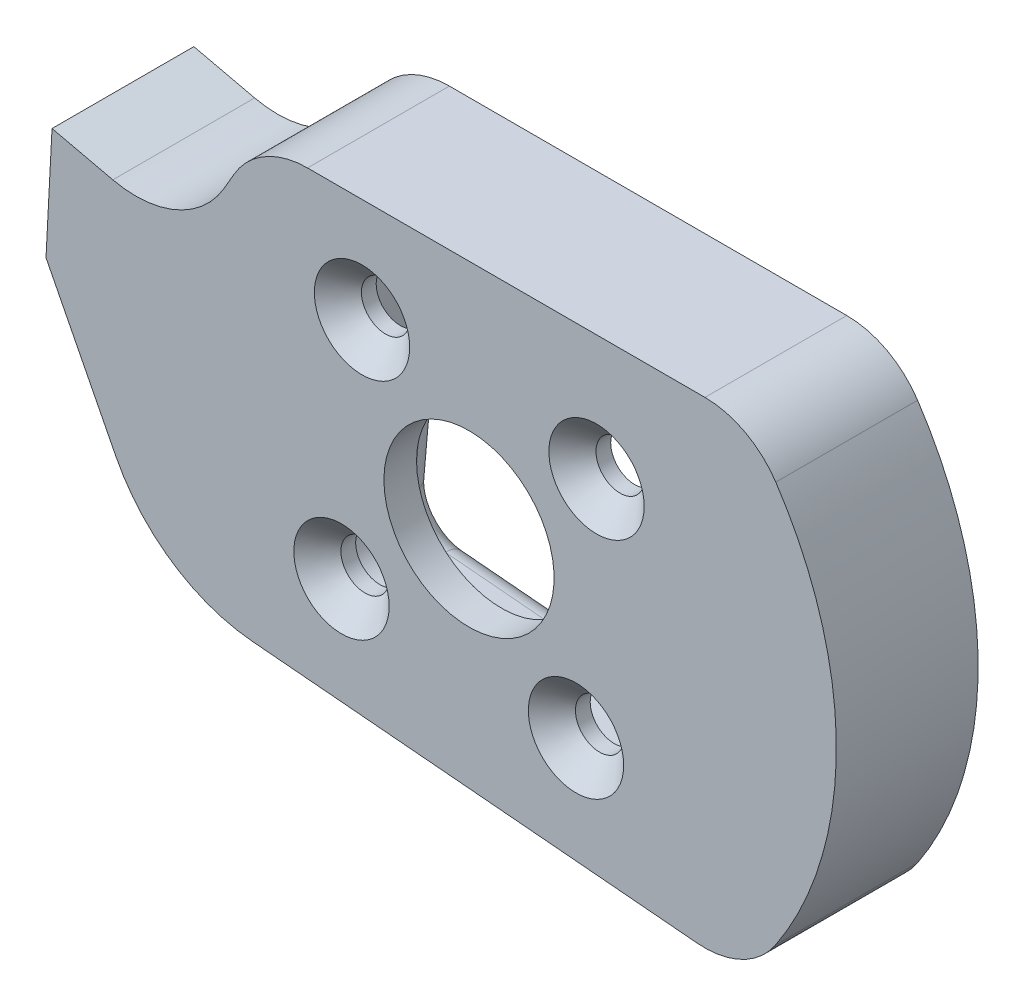
SolidWorks part; units mm, degrees
material "AISI 4340 Aço, normalizado"
ref_plane "Plano frontal" through (0, 0, 0) normal (0, 0, 1) x (1, 0, 0)
ref_plane "Plano superior" through (0, 0, 0) normal (0, 1, 0) x (1, 0, 0)
ref_plane "Plano direito" through (0, 0, 0) normal (1, 0, 0) x (0, 0, -1)
other "Center of Mass"
sketch "Sketch2" plane through (0, 0, 0) normal (0, 0, 1) x (1, 0, 0)
  line L0 (0, 0) -> (-50, 0) construction
  line L1 (-127.5781, 46.0511) -> (-149.0143, 51)
  line L2 (0, 0) -> (-155.9672, 21.9198) construction
  line L5 (-58.9322, 84) -> (81.1804, 84)
  line L6 (0, 0) -> (0, 41.2714) construction
  line L8 (-84.913, 69) -> (-88.303, 63.1284)
  line L14 (-78.3219, -70.2808) -> (78.4896, -84)
  line L19 (-149.0143, 51) -> (-151.1368, 10.5)
  line L20 (-149.5248, 48.7888) -> (-147.8193, 56.1762) construction
  line L22 (-151.1368, 10.5) -> (-126.5529, -37.7485)
  circle A0 centre (0, 0) radius 157.5 construction
  arc A5 (81.1804, 84) -> (106.1589, 70.6154) centre (81.1804, 54) cw
  arc A6 (-58.9322, 84) -> (-84.913, 69) centre (-58.9322, 54) ccw
  arc A17 (-126.5529, -37.7485) -> (-78.3219, -70.2808) centre (-73.0925, -10.5091) ccw
  arc A18 (-127.5781, 46.0511) -> (-88.303, 63.1284) centre (-119.4799, 81.1284) ccw
  arc A20 (106.1589, 70.6154) -> (106.0595, -70.7647) centre (0, 0) cw
  arc A21 (78.4896, -84) -> (106.0595, -70.7647) centre (81.1043, -54.1142) ccw
  point P29 (-157.5, 0)
  point P31 (29.3939, 84)
  point P32 (-76.2527, 84)
  point P33 (106.1589, -70.6154)
  dimension "D1" = 315
  dimension "D4" = 30
  dimension "D5" = 36
  dimension "D13" = 30
  dimension "D11" = 60
  dimension "D10" = 84
  dimension "D2" = 5
  dimension "D3" = 10
  dimension "D7" = 30
  dimension "D8" = 77
  dimension "D12" = 30
  dimension "D9" = 51
  dimension "D14" = 40.5
  dimension "D15" = 22
  dimension "D6" = 30
  dimension "D16" = 5
  dimension "D17" = 84
extrude "EXTRUSÃO PRINCIPAL" add sketch "Sketch2" along normal blind 50 contours L5 A5 A20 A21 L14 A17 L22 L19 L1 A18 L8 A6
other "Ponto de referência do centro da massa1"
ref_plane "Plano2" through (0, 2.2662, 0) normal (0, -1, 0) x (-1, 0, 0)
ref_plane "Plano3" through (-2.0065, 0, 0) normal (1, 0, 0) x (0, 0, -1)
sketch "Esboço2" plane through (0, 0, 0) normal (0, 0, -1) x (-1, 0, 0)
  line L0 (-8.25, 2.2662) -> (8.25, 2.2662) construction
  line L1 (-48.3318, 55.5818) -> (42.3219, 63.513)
  line L2 (-59.2402, 42.5816) -> (-51.3091, -48.0721)
  line L3 (-38.3089, -58.9806) -> (52.3449, -51.0494)
  line L4 (55.3221, 52.6045) -> (63.2533, -38.0492)
  line L5 (-60.2861, 54.5359) -> (64.2992, -50.0035) construction
  line L6 (-50.2632, -60.0265) -> (54.2763, 64.5588) construction
  line L7 (2.0065, 8.25) -> (2.0065, -8.25) construction
  line L8 (78.3219, -70.2808) -> (-78.4896, -84) construction
  line L10 (2.503, 2.2662) -> (86.0271, 2.2662) construction
  circle A0 centre (2.0065, 2.2662) radius 30
  arc A2 (-48.3318, 55.5818) -> (-59.2402, 42.5816) centre (-47.2859, 43.6275) ccw
  arc A3 (42.3219, 63.513) -> (55.3221, 52.6045) centre (43.3678, 51.5586) cw
  arc A4 (52.3449, -51.0494) -> (63.2533, -38.0492) centre (51.299, -39.0951) ccw
  arc A5 (-51.3091, -48.0721) -> (-38.3089, -58.9806) centre (-39.3547, -47.0263) ccw
  circle A6 centre (2.0065, 2.2662) radius 42.5
  circle A7 centre (2.0065, 2.2662) radius 37.5
  circle A8 centre (2.0065, 2.2662) radius 27 construction
  dimension "D1" = 12
  dimension "D5" = 85
  dimension "D6" = 75
  dimension "D7" = 54
  dimension "D3" = 115
  dimension "D4" = 115
  dimension "D2" = 3
extrude "REBAIXO CAMISA" cut sketch "Esboço2" against normal blind 36.5 contours L1 A3 L4 A4 L3 A5 L2 A2
fillet "FILETE ALIVIO REBAIXO" radius 8 8 edges at (56.4784, 51.3409, 0) (55.2747, -2.7453, 0) (47.0682, -56.2188, 0) (-7.018, -55.015, 0) (-60.4915, -46.8085, 0) (-59.2877, 7.2776, 0) (-51.0813, 60.7512, 0) (3.0049, 59.5474, 0)
extrude "FURO EIXO" cut sketch "Esboço2<3>" against normal through all contours A0
sketch "Esboço2<3>" plane through (0, 0, 0) normal (0, 0, -1) x (-1, 0, 0) same geometry as "Esboço2"
extrude "Corte-extrusão1" cut sketch "Esboço2<4>" against normal blind 2 from surface contours A7 starting at face at (-32.0065, 2.2662, 36.5)
sketch "Esboço2<4>" plane through (0, 0, 0) normal (0, 0, -1) x (-1, 0, 0) same geometry as "Esboço2"
sketch "Esboço3" plane through (0, 0, 50) normal (0, 0, 1) x (1, 0, 0)
  line L0 (-78.3219, -70.2808) -> (78.4896, -84) construction
  line L1 (-46.9656, -35.4589) -> (35.7186, -42.6929) construction
  line L2 (-46.9656, -35.4589) -> (-39.7317, 47.2252) construction
  line L3 (-39.7317, 47.2252) -> (42.9525, 39.9913) construction
  line L4 (35.7186, -42.6929) -> (42.9525, 39.9913) construction
  line L5 (-46.9656, -35.4589) -> (42.9525, 39.9913) construction
  line L6 (-39.7317, 47.2252) -> (35.7186, -42.6929) construction
  circle A0 centre (-2.0065, 2.2662) radius 30 construction
  point P0 (-2.0065, 2.2662)
  point P5 (0, 0)
  point P10 (54.6221, 46.7806)
  point P11 (-63.5041, -41.179)
  point P12 (56.5274, -48.1649)
  point P13 (41.2853, -56.7386)
  dimension "D1" = 83
hole_wizard "Escareado para parafuso Allen sextavado escareado de M161" positions "Esboço4" profile "Esboço7" countersink size "M16" standard "ISO" end condition through all
sketch "Esboço4" plane through (0, 0, 50) normal (0, 0, 1) x (1, 0, 0)
  point P0 (-39.7317, 47.2252)
  point P3 (42.9525, 39.9913)
  point P6 (-46.9656, -35.4589)
  point P9 (35.7186, -42.6929)
sketch "Esboço7" plane through (-39.7317, 47.2252, 50) normal (1, 0, 0) x (0, -1, 0)
  line L0 (0, 0) -> (0, 50)
  line L1 (0, 50) -> (8.5, 50)
  line L2 (8.5, 50) -> (8.5, 8.3)
  line L3 (8.5, 8.3) -> (16.8, 0)
  line L5 (16.8, 0) -> (0, 0)
  line L6 (-8.5, 8.3) -> (-16.8, 0) construction
  line L11 (0, -6.35) -> (0, 107.95) construction
  dimension "Thru Hole Dia." = 17
  dimension "Thru Hole Depth" = 50
  dimension "Near C'Sink Dia." = 33.6
  dimension "Near C'Sink Angle" = 90
chamfer "CHANFRO CAMISA" [suppressed] distance 1 angle 45
sketch "REF. POLIA" plane through (0, 0, 0) normal (0, 0, -1) x (-1, 0, 0)
  circle A0 centre (1.8584, 2.135) radius 71
  circle A1 centre (1.8584, 2.135) radius 30 construction
  dimension "D1" = 142
equation "\"escala\"= 1                        'projeto - escala geral"
equation "\"escala_disco-arma\"= 3                                                                  'disco arma - escala geometria disco arma"
equation "\"rolamento_D-ext\"= 85               'rolamento arma - diametro externo"
equation "\"rolamento_d-int\"= 45               'rolamento arma - diametro interno"
equation "\"rolamento_b-esp\"= 23               'rolamento arma - espessura"
equation "\"arma_rebaixo-camisa_b\"= \"rolamento_b-esp\" + (\"arma-espessura\"-\"rolamento_b-esp\")/2     'disco arma - profundidade rebaixo camisa"
equation "\"arma-espessura\"= 50                                                                    'disco arma - espessura disco arma"
equation "\"D1@EXTRUSÃO PRINCIPAL\" = \"arma-espessura\""
equation "\"eixo_diam\"= \"rolamento_d-int\"      'eixo arma - diametro"
equation "\"camisa_largura\"=115                                                        'camisa arma - tamanho do lado"
equation "\"D3@Esboço2\"=\"camisa_largura\""
equation "\"camisa_raio\"= 16                                                           'camisa arma - raio canto interno"
equation "\"arma_rebaixo-camisa_raio\"= 12                                                         'disco arma - raio do rebaixo da camisa da arma "
equation "\"D1@Esboço2\"=\"arma_rebaixo-camisa_raio\""
equation "\"arma_alivio_raio\"= 12 * \"escala_disco-arma\""
equation "\"arma_diam_max\"= 105 * \"escala_disco-arma\""
equation "\"D1@Sketch2\" = \"arma_diam_max\""
equation "\"arma_arestas_raio\"= 10 * \"escala_disco-arma\""
equation "\"D4@Sketch2\" = \"arma_arestas_raio\""
equation "\"arma_altura_superior-centro\"= 28 * \"escala_disco-arma\""
equation "\"D10@Sketch2\" = \"arma_altura_superior-centro\""
equation "\"arma_dente_raio\"= 12 * \"escala_disco-arma\""
equation "\"D5@Sketch2\" = \"arma_dente_raio\""
equation "\"arma_altura_dente-centro\"= 17 * \"escala_disco-arma\""
equation "\"D9@Sketch2\"=\"arma_altura_dente-centro\""
equation "\"arma_dente_altura\"= 13.5 * \"escala_disco-arma\""
equation "\"arma_alivio-dente_raio\"= 20 * \"escala_disco-arma\""
equation "\"arma_traseira_offset\"= 10 * \"escala_disco-arma\""
equation "\"arma_centralizacao_offset\"= 8 * \"escala_disco-arma\""
equation "\"arma_eixo-furo_folga\"= 4                                                              'disco arma - folga entre furo arma e eixo"
equation "\"D1@REBAIXO CAMISA\" = \"arma_rebaixo-camisa_b\""
equation "\"D6@Sketch2\"=\"arma_traseira_offset\""
equation "\"D11@Sketch2\"=\"arma_alivio-dente_raio\""
equation "\"D4@Esboço2\"=\"camisa_largura\""
equation "\"D14@Sketch2\"=\"arma_dente_altura\""
equation "\"arma_altura_inferior-centro\"= 28 * \"escala_disco-arma\""
equation "\"D17@Sketch2\"=\"arma_altura_inferior-centro\""
equation "\"D13@Sketch2\"=\"arma_arestas_raio\""
equation "\"D5@Esboço2\"=\"rolamento_D-ext\""
equation "\"polia_diam_eff\"= 142"
equation "\"D1@REF. POLIA\" = \"polia_diam_eff\""
equation "\"arma_dente_comprimento\"=22"
equation "\"D15@Sketch2\"=\"arma_dente_comprimento\""
equation "\"camisa_rebaixo_rolamento\"= 1 * \"rolamento_b-esp\""
equation "\"polia_espessura\"= 40  "
equation "\"rolamento_D1-ext\"= 75             'rolamento arma - ressalto diam externo"
equation "\"rolamenot_d2-int\" = 54             'rolamento arma - ressalto diam interno"
equation "\"camisa_raio-alivio\"= 6                                                    'camisa arma - raio de alivio de tensoes no encaixe da arma"
equation "\"camisa_comprimento-centro\"= 2*(\"arma_rebaixo-camisa_b\")+\"polia_espessura\" "
equation "\"camisa_furos_dist\"= 83"
equation "\"camisa_furos_prof\"= 30"
equation "\"D1@FILETE ALIVIO REBAIXO\" = \"camisa_raio-alivio\" + 2"
equation "\"D6@Esboço2\"=\"rolamento_D1-ext\""
equation "\"D7@Esboço2\"=\"rolamenot_d2-int\""
equation "\"D1@Esboço3\"=\"camisa_furos_dist\""
